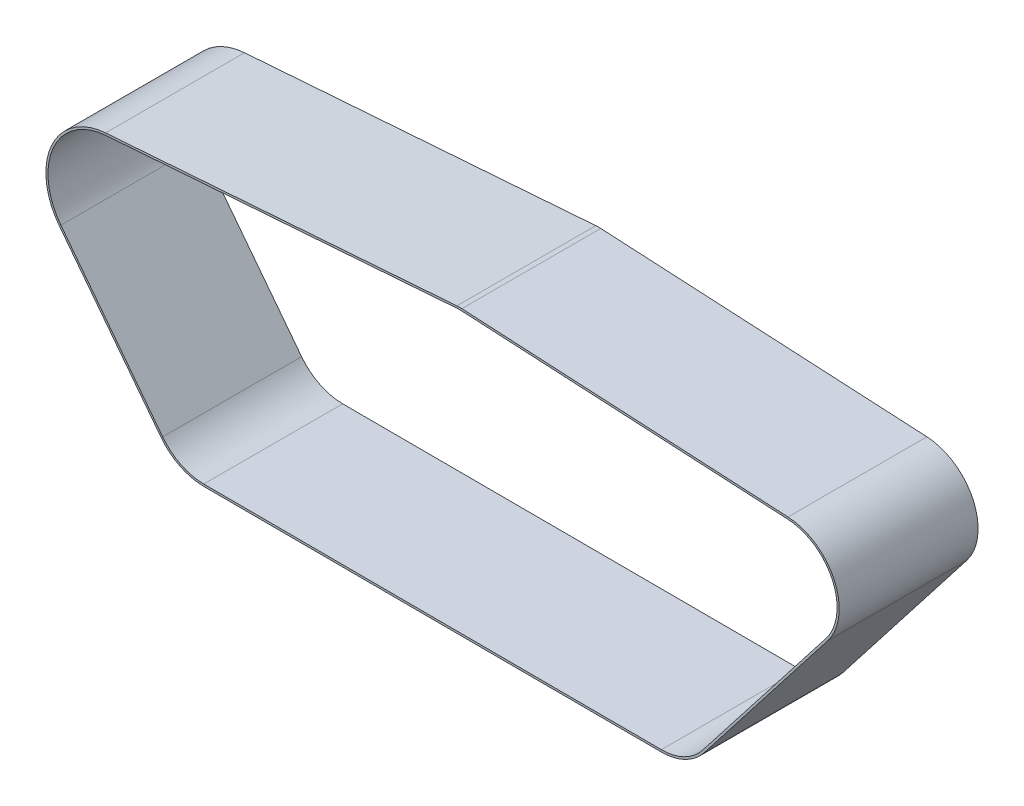
SolidWorks part; units mm, degrees
ref_plane "Front Plane" through (0, 0, 0) normal (0, 0, 1) x (1, 0, 0)
ref_plane "Top Plane" through (0, 0, 0) normal (0, 1, 0) x (1, 0, 0)
ref_plane "Right Plane" through (0, 0, 0) normal (1, 0, 0) x (0, 0, -1)
sketch "Sketch2" plane through (0, 0, 0) normal (0, 0, 1) x (1, 0, 0)
  line L0 (0, 0) -> (1, 0) construction
  line L1 (0, 0) -> (0, 1) construction
  line L2 (-1.551, 21.0429) -> (117.315, 29.804)
  line L3 (118.91, 29.8203) -> (229.2625, 23.9536)
  line L4 (242.2162, -4.4327) -> (200.3827, -58.1721)
  line L5 (186.4458, -64.9609) -> (31.6219, -64.5311)
  line L6 (17.7184, -57.6592) -> (-16.727, -12.8615)
  arc A0 (-16.727, -12.8615) -> (-1.551, 21.0429) centre (0, 0) cw
  arc A1 (117.315, 29.804) -> (118.91, 29.8203) centre (118.2411, 17.238) cw
  arc A2 (229.2625, 23.9536) -> (242.2162, -4.4327) centre (228.3281, 6.3784) cw
  arc A3 (200.3827, -58.1721) -> (186.4458, -64.9609) centre (186.4947, -47.3609) cw
  arc A4 (31.6219, -64.5311) -> (17.7184, -57.6592) centre (31.6707, -46.9312) cw
extrude "Extrude-Thin1" add sketch "Sketch2" along normal mid plane 47 thin thin type one direction wall 0.7
sketch "Sketch3" plane through (0, 0, 23.5) normal (0, 0, 1) x (1, 0, 0)
  line L5 (31.6219, -64.5311) -> (186.4458, -64.9609)
  line L6 (200.3827, -58.1721) -> (242.2162, -4.4327)
  line L7 (229.2625, 23.9536) -> (118.91, 29.8203)
  line L8 (117.315, 29.804) -> (-1.551, 21.0429)
  line L9 (-16.727, -12.8615) -> (17.7184, -57.6592)
  line L10 (31.6219, -64.5311) -> (186.4458, -64.9609)
  line L11 (200.3827, -58.1721) -> (242.2162, -4.4327)
  line L12 (229.2625, 23.9536) -> (118.91, 29.8203)
  line L13 (117.315, 29.804) -> (-1.551, 21.0429)
  line L14 (-16.727, -12.8615) -> (17.7184, -57.6592)
  arc A5 (186.4458, -64.9609) -> (200.3827, -58.1721) centre (186.4947, -47.3609) ccw
  arc A6 (242.2162, -4.4327) -> (229.2625, 23.9536) centre (228.3281, 6.3784) ccw
  arc A7 (118.91, 29.8203) -> (117.315, 29.804) centre (118.2411, 17.238) ccw
  arc A8 (-1.551, 21.0429) -> (-16.727, -12.8615) centre (0, 0) ccw
  arc A9 (17.7184, -57.6592) -> (31.6219, -64.5311) centre (31.6707, -46.9312) ccw
  arc A10 (186.4458, -64.9609) -> (200.3827, -58.1721) centre (186.4947, -47.3609) ccw
  arc A11 (242.2162, -4.4327) -> (229.2625, 23.9536) centre (228.3281, 6.3784) ccw
  arc A12 (118.91, 29.8203) -> (117.315, 29.804) centre (118.2411, 17.238) ccw
  arc A13 (-1.551, 21.0429) -> (-16.727, -12.8615) centre (0, 0) ccw
  arc A14 (17.7184, -57.6592) -> (31.6219, -64.5311) centre (31.6707, -46.9312) ccw
  dimension "D1" = 0
